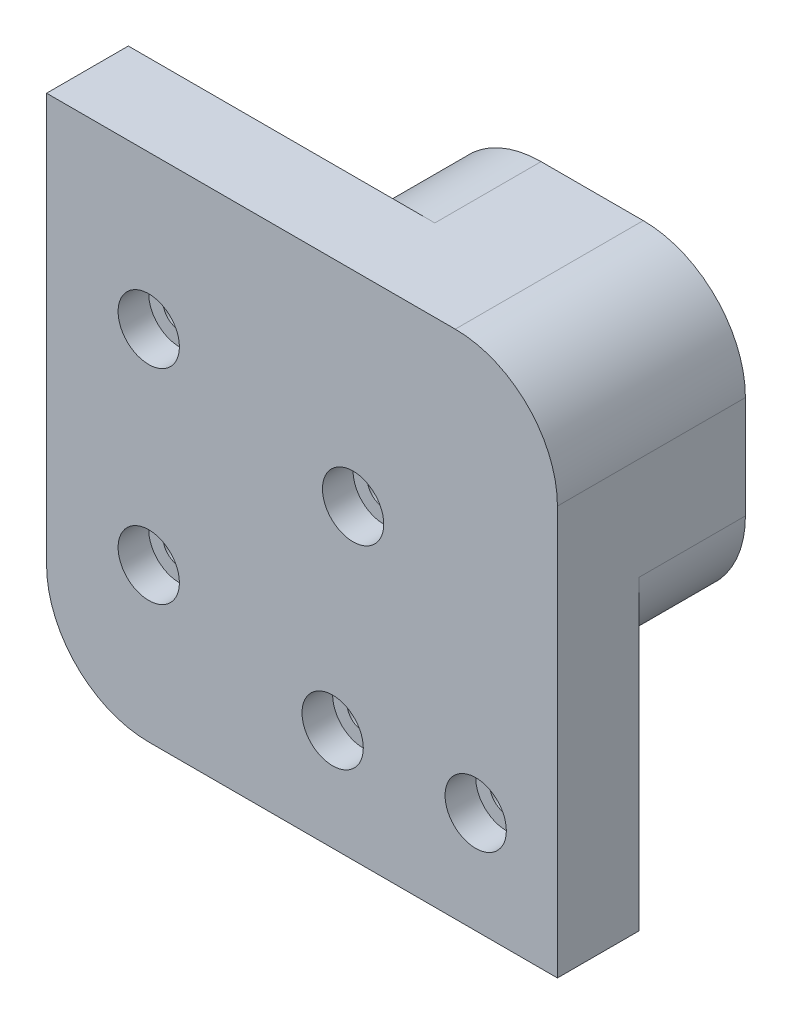
SolidWorks part; units mm, degrees
ref_plane "前视基准面" through (0, 0, 0) normal (0, 0, 1) x (1, 0, 0)
ref_plane "上视基准面" through (0, 0, 0) normal (0, 1, 0) x (1, 0, 0)
ref_plane "右视基准面" through (0, 0, 0) normal (1, 0, 0) x (0, 0, -1)
other "Configuration Table"
sketch "草图1" plane through (0, 0, 0) normal (0, 0, 1) x (1, 0, 0)
  line L0 (-10, 77.5) -> (-10, -160) construction
  line L1 (-10, -110) -> (10, -110)
  line L2 (-10, -110) -> (-10, -160)
  line L4 (10, -110) -> (10, -140.0288)
  line L5 (-10, -160) -> (40, -160)
  line L7 (10, -140.0288) -> (40, -140.0288)
  line L8 (40, -160) -> (40, -140.0288)
  line L9 (184.3942, -160) -> (10.0042, -160) construction
  line L10 (10, -130.0288) -> (10, 47.5288) construction
  line L11 (174.3942, -140.0288) -> (20, -140.0288) construction
  circle A0 centre (0, -125) radius 1.6
  circle A1 centre (0, -145) radius 1.6
  circle A2 centre (18, -150.0144) radius 1.6
  circle A3 centre (32, -150.0144) radius 1.6
  point P22 (0, -110)
  point P23 (40, -150.0144)
  dimension "D2" = 3.2
  dimension "D4" = 15
  dimension "D1" = 50
  dimension "D3" = 15
  dimension "D5" = 8
  dimension "D6" = 8
extrude "凸台-拉伸1" add sketch "草图1" along normal blind 8
sketch "草图2" plane through (0, 0, 8) normal (0, 0, 1) x (1, 0, 0)
  circle A0 centre (32, -150.0144) radius 3
  circle A1 centre (32, -150.0144) radius 1.6
  circle A2 centre (32, -150.0144) radius 1.6 construction
  circle A3 centre (18, -150.0144) radius 1.6
  circle A4 centre (18, -150.0144) radius 1.6 construction
  circle A5 centre (0, -145) radius 1.6
  circle A6 centre (0, -145) radius 1.6 construction
  circle A7 centre (0, -125) radius 1.6
  circle A8 centre (0, -125) radius 1.6 construction
  circle A9 centre (18, -150.0144) radius 3
  circle A10 centre (0, -145) radius 3
  circle A11 centre (0, -125) radius 3
  dimension "D1" = 6
  dimension "D2" = 0
  dimension "D3" = 0
  dimension "D4" = 0
  dimension "D5" = 0
extrude "切除-拉伸1" cut sketch "草图2" against normal blind 3
fillet "圆角1" radius 10 2 edges at (10, -140.0288, 4) (-10, -160, 4)
sketch "草图3" plane through (0, 0, 8) normal (0, 0, 1) x (1, 0, 0)
  line L0 (10, -130.0288) -> (10, -110) construction
  line L1 (40, -140.0288) -> (20, -140.0288) construction
  line L2 (10, -130.0288) -> (10, -110)
  line L3 (40, -140.0288) -> (20, -140.0288)
  line L4 (40, -140.0288) -> (40, -110)
  line L5 (40, -110) -> (10, -110)
  arc A0 (10, -130.0288) -> (20, -140.0288) centre (20, -130.0288) ccw construction
  arc A1 (10, -130.0288) -> (20, -140.0288) centre (20, -130.0288) ccw
  circle A2 centre (20, -130.0288) radius 2.05 construction
  arc A3 (20, -127.9788) -> (22.05, -130.0288) centre (20, -130.0288) ccw construction
  circle A4 centre (20, -130.0288) radius 2.05 construction
  arc A5 (20, -127.9788) -> (22.05, -130.0288) centre (20, -130.0288) ccw
  circle A6 centre (20, -130.0288) radius 1.6
  dimension "D1" = 3.2
extrude "凸台-拉伸2" add sketch "草图3" against normal up to surface (18.3999 mm away) contours L4 L5 A6 region at (25.3606, -124.6534, 8)
sketch "草图4" plane through (0, 0, 8) normal (0, 0, 1) x (1, 0, 0)
  circle A0 centre (20, -130.0288) radius 1.6 construction
  circle A1 centre (20, -130.0288) radius 1.6 construction
  circle A2 centre (20, -130.0288) radius 3
  dimension "D1" = 6
extrude "切除-拉伸2" cut sketch "草图4" against normal blind 3
fillet "圆角2" radius 10 3 edges at (40, -140.0288, -5.2) (10, -110, -5.2) (40, -110, -1.2)
